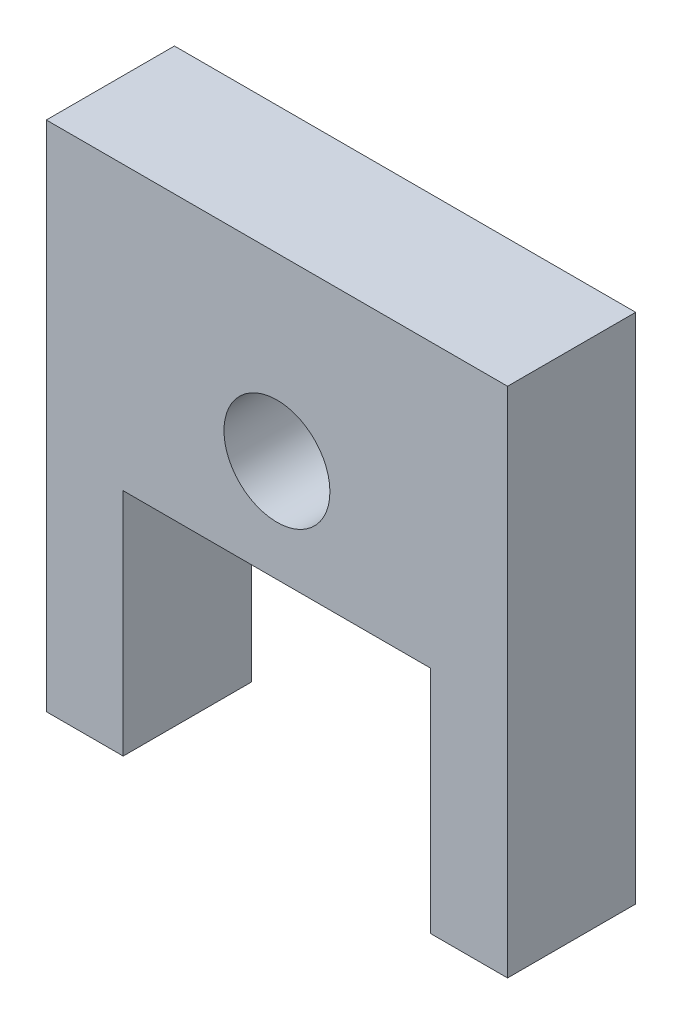
SolidWorks part; units mm, degrees
ref_plane "Front Plane" through (0, 0, 0) normal (0, 0, 1) x (1, 0, 0)
ref_plane "Top Plane" through (0, 0, 0) normal (0, 1, 0) x (1, 0, 0)
ref_plane "Right Plane" through (0, 0, 0) normal (1, 0, 0) x (0, 0, -1)
sketch "Sketch1" plane through (0, 0, 0) normal (0, 0, 1) x (1, 0, 0)
  line L0 (2.75, 0) -> (-2.75, 0) construction
  line L1 (0, 0) -> (3, 0)
  line L2 (18, 0) -> (18, 20)
  line L3 (18, 20) -> (0, 20)
  line L4 (0, -2.75) -> (0, 2.75) construction
  line L5 (0, 20) -> (0, 0)
  line L6 (3, 0) -> (3, 8.97)
  line L7 (3, 8.97) -> (15, 8.97)
  line L8 (15, 8.97) -> (15, 0)
  line L9 (15, 0) -> (18, 0)
  dimension "D1" = 18
  dimension "D2" = 20
  dimension "D3" = 12
  dimension "D4" = 3
  dimension "D5" = 8.97
extrude "Boss-Extrude1" add sketch "Sketch1" along normal blind 5
sketch "Sketch3" plane through (0, 0, 5) normal (0, 0, 1) x (1, 0, 0)
  line L0 (9, 8.97) -> (9, 22.3726) construction
  line L1 (3, 8.97) -> (15, 8.97) construction
  circle A0 centre (9, 12.97) radius 2.0675
  dimension "D1" = 4
extrude "Cut-Extrude1" cut sketch "Sketch3" against normal through all
